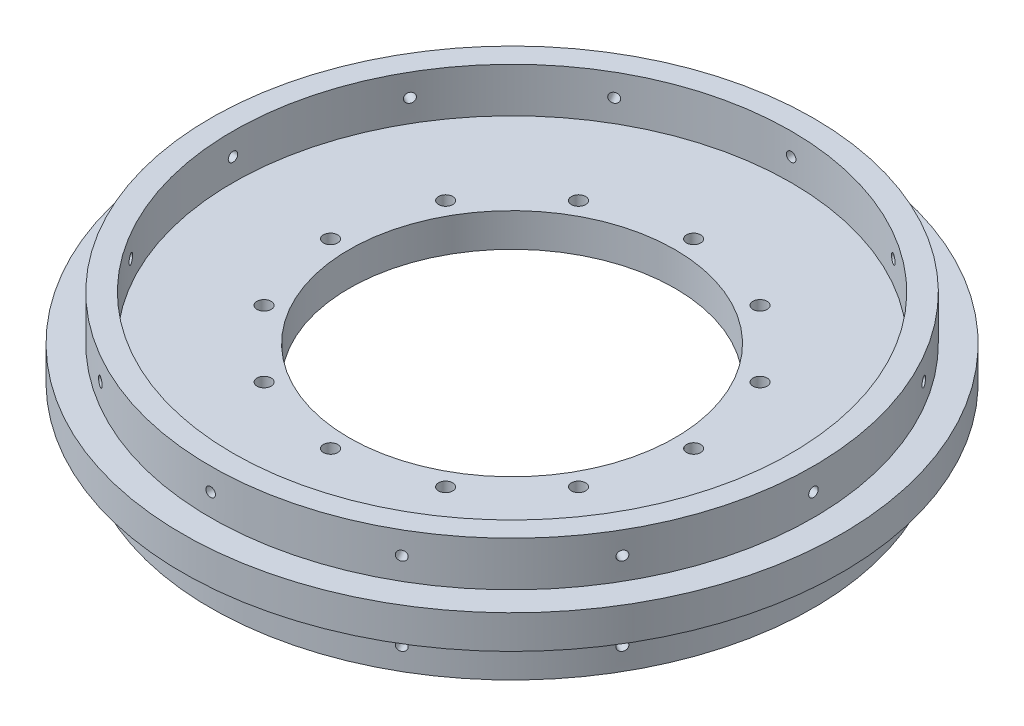
SolidWorks part; units mm, degrees
material "6061-T6 (SS)"
ref_plane "Front Plane" through (0, 0, 0) normal (0, 0, 1) x (1, 0, 0)
ref_plane "Top Plane" through (0, 0, 0) normal (0, 1, 0) x (1, 0, 0)
ref_plane "Right Plane" through (0, 0, 0) normal (1, 0, 0) x (0, 0, -1)
sketch "Sketch1" plane through (0, 0, 0) normal (0, 1, 0) x (1, 0, 0)
  line L5 (0, 0) -> (127.635, 0)
  line L6 (0, 0) -> (0, 127.635)
  line L7 (0, 127.635) -> (127.635, 127.635)
  line L8 (127.635, 0) -> (127.635, 127.635)
  dimension "D1" = 127.635
  dimension "D2" = 127.635
extrude "Boss-Extrude1" add sketch "Sketch1" along normal blind 9.525 contours L5 L8 L7 L6
sketch "Sketch12" plane through (0, 0, 0) normal (0, -1, 0) x (1, 0, 0)
  line L0 (63.8175, 0) -> (63.8175, -127.635) construction
  line L1 (0, 0) -> (127.635, 0) construction
  line L2 (0, -127.635) -> (127.635, -127.635) construction
  line L3 (0, -63.8175) -> (127.635, -63.8175) construction
  line L4 (0, 0) -> (0, -127.635) construction
  line L5 (127.635, 0) -> (127.635, -127.635) construction
  circle A0 centre (63.8175, -63.8175) radius 93.726
  dimension "D1" = 187.452
extrude "Boss-Extrude2" add sketch "Sketch12" against normal up to surface (9.525 mm away) contours A0 up to face at (63.8175, 9.525, -63.8175)
sketch "Sketch5" plane through (0, 9.525, 0) normal (0, 1, 0) x (1, 0, 0)
  circle A0 centre (63.8175, 63.8175) radius 46.355
  circle A3 centre (63.8175, 63.8175) radius 93.726 construction
  dimension "D1" = 92.71
extrude "Cut-Extrude1" cut sketch "Sketch5" against normal blind 9.525
sketch "Sketch11" plane through (0, 9.525, 0) normal (0, 1, 0) x (1, 0, 0)
  line L0 (63.8175, 63.8175) -> (63.8175, 115.443) construction
  circle A0 centre (63.8175, 115.443) radius 2.0193
  dimension "D2" = 4.0386
  dimension "D1" = 51.6255
extrude "Cut-Extrude3" cut sketch "Sketch11" against normal through all contours A0
pattern_circular "CirPattern1" count 12 over 360 about axis through (63.8175, 9.525, -63.8175) along (0, 1, 0) of "Cut-Extrude3"
sketch "Sketch14" plane through (0, 9.525, 0) normal (0, -1, 0) x (1, 0, 0)
  line L0 (63.8175, -63.8175) -> (147.6375, -63.8175) construction
  line L1 (0, -5.2388) -> (0, 5.2388) construction
  line L2 (147.6375, -63.8175) -> (152.7175, -63.8175)
  line L3 (136.3808, -105.7742) -> (140.8401, -108.2104)
  circle A0 centre (63.8175, -63.8175) radius 46.355 construction
  arc A2 (147.6375, -63.8175) -> (136.3808, -105.7742) centre (63.8175, -63.8175) cw
  arc A3 (152.7175, -63.8175) -> (140.8401, -108.2104) centre (63.8175, -63.8175) cw
  point P0 (63.8175, -63.8175)
  dimension "D1" = 83.82
  dimension "D2" = 88.9
  dimension "D3" = 46.482
  dimension "D4" = 43.942
ref_plane "Support mirror reference plane" through (0, 4.7625, 0) normal (0, 1, 0) x (1, 0, 0)
sketch "Sketch25" plane through (0, 9.525, 0) normal (0, -1, 0) x (1, 0, 0)
  line L0 (63.8175, -63.8175) -> (123.0872, -4.5478) construction
  line L2 (123.0872, -4.5478) -> (126.6793, -0.9557)
  line L3 (144.7953, -42.1754) -> (149.6712, -40.7448)
  line L5 (63.8175, -63.8175) -> (147.6375, -63.8175) construction
  arc A2 (123.0872, -4.5478) -> (144.7953, -42.1754) centre (63.8175, -63.8175) cw
  arc A3 (126.6793, -0.9557) -> (149.6712, -40.7448) centre (63.8175, -63.8175) cw
  point P0 (63.8175, -63.8175)
  dimension "D1" = 83.82
  dimension "D2" = 88.9
  dimension "D3" = 46.482
  dimension "D4" = 43.942
  dimension "D5" = 45
sketch "Sketch30" plane through (0, 0, 0) normal (0, -1, 0) x (1, 0, 0)
  circle A0 centre (63.8175, -63.8175) radius 85.725
  circle A1 centre (63.8175, -63.8175) radius 79.375
  dimension "D1" = 171.45
  dimension "D2" = 158.75
extrude "Boss-Extrude3" add sketch "Sketch30" along normal blind 12.7
mirror "Mirror1" about plane through (0, 4.7625, 0) normal (0, 1, 0) of "Boss-Extrude3"
sketch "Sketch31" plane through (0, 0, 0) normal (0, -1, 0) x (-1, 0, 0)
  line L0 (-63.8175, -52.481) -> (-63.8175, 177.7216) construction
ref_plane "Plane1" through (0, 0, -149.5425) normal (0, 0, -1) x (-1, 0, 0)
ref_plane "Plane2" through (63.8175, 0, 0) normal (-1, 0, 0) x (0, 0, -1)
sketch "Sketch32" plane through (0, 0, -149.5425) normal (0, 0, -1) x (-1, 0, 0)
  line L4 (-63.8175, -87.3125) -> (-63.8175, 87.3125) construction
  line L5 (-149.5425, 0) -> (21.9075, 0) construction
  line L6 (21.9075, 9.525) -> (-149.5425, 9.525) construction
  circle A0 centre (-63.8175, -6.35) radius 1.3526
  circle A1 centre (-63.8175, 15.875) radius 1.3525
  dimension "D1" = 2.7051
  dimension "D2" = 2.7051
  dimension "D3" = 6.35
  dimension "D4" = 6.35
extrude "Cut-Extrude4" cut sketch "Sketch32" against normal blind 15.24
pattern_circular "CirPattern2" count 12 over 360 about axis through (63.8175, -12.7, -63.8175) along (0, 1, 0) of "Cut-Extrude4"
